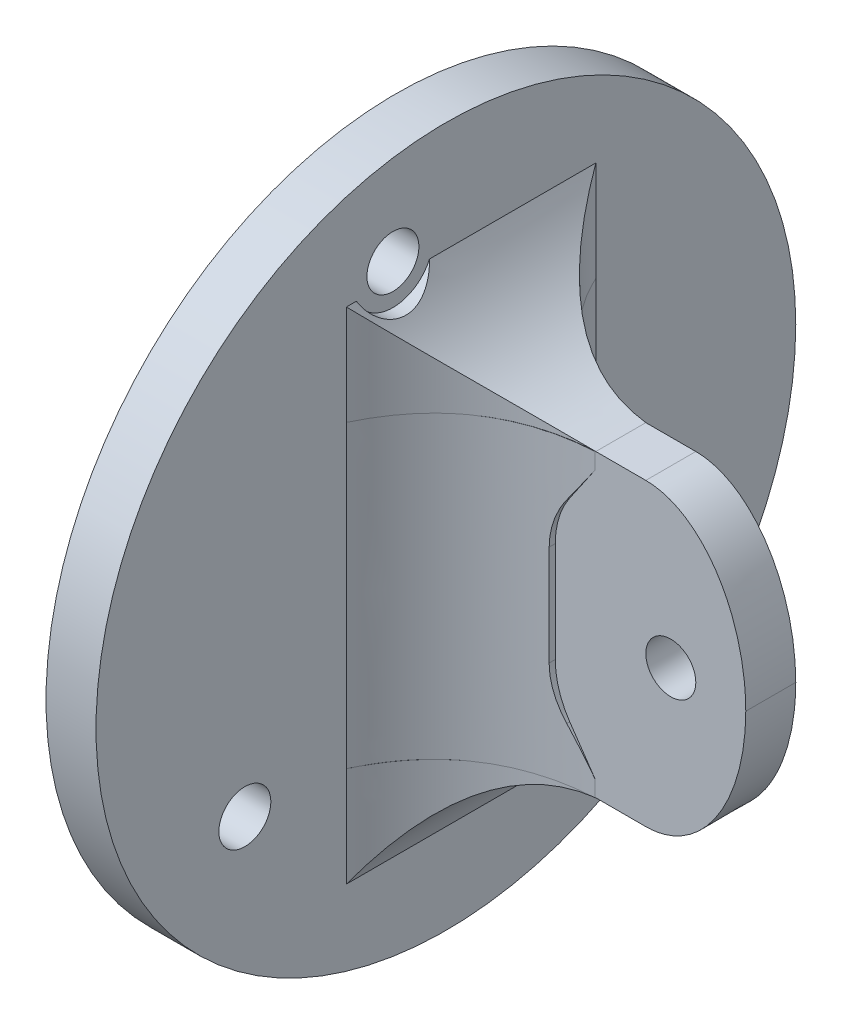
SolidWorks part; units mm, degrees
ref_plane "Ebene vorne" through (0, 0, 0) normal (0, 0, 1) x (1, 0, 0)
ref_plane "Ebene oben" through (0, 0, 0) normal (0, 1, 0) x (1, 0, 0)
ref_plane "Ebene rechts" through (0, 0, 0) normal (1, 0, 0) x (0, 0, -1)
sketch "Skizze1" plane through (0, 0, 0) normal (1, 0, 0) x (0, 0, -1)
  line L5 (-48.2966, 43.3868) -> (51.7034, 43.3868)
  line L6 (-48.2966, 43.3868) -> (-48.2966, -56.6132)
  line L7 (-48.2966, -56.6132) -> (51.7034, -56.6132)
  line L8 (51.7034, 43.3868) -> (51.7034, -56.6132)
  dimension "D1" = 100
  dimension "D2" = 100
extrude "Aufsatz-Linear austragen1" add sketch "Skizze1" along normal blind 5
sketch "Skizze4" plane through (0, 0, 0) normal (-1, 0, 0) x (0, 0, 1)
  line L1 (-51.7034, -56.6132) -> (-51.7034, 43.3868) construction
  circle A0 centre (3.5966, 30) radius 2.6
  circle A1 centre (18.4065, -10.6899) radius 2.6
  circle A2 centre (-24.2369, -3.1707) radius 2.6
  point P12 (-0.7446, 5.3798)
  point P13 (-1.7034, 0)
  dimension "D1" = 5.2
  dimension "D2" = 30
  dimension "D3" = 55.3
  dimension "D4" = 3
extrude "Schnitt-Linear austragen1" cut sketch "Skizze4" against normal blind 10
ref_plane "Ebene1" through (0, 0, -1.7034) normal (0, 0, -1) x (-1, 0, 0)
ref_plane "Ebene2" through (0, -6.6132, 0) normal (0, 1, 0) x (1, 0, 0)
sketch "Skizze5" plane through (5, 0, 0) normal (1, 0, 0) x (0, 0, -1)
  line L0 (1.7034, -2.75) -> (1.7034, 2.75) construction
  line L4 (2.75, -6.6132) -> (-2.75, -6.6132) construction
  line L5 (-48.2966, 43.3868) -> (51.7034, 43.3868)
  line L6 (51.7034, 43.3868) -> (51.7034, -56.6132)
  line L7 (51.7034, -56.6132) -> (-48.2966, -56.6132)
  line L8 (-48.2966, -56.6132) -> (-48.2966, 43.3868)
  circle A1 centre (1.7034, 4.3868) radius 35
  dimension "D1" = 70
  dimension "D2" = 0
  dimension "D3" = 11
extrude "Schnitt-Linear austragen2" cut sketch "Skizze5" against normal blind 10
sketch "Skizze6" plane through (5, 0, 0) normal (1, 0, 0) x (0, 0, -1)
  line L0 (1.7034, -55) -> (1.7034, 55) construction
  line L1 (1.7034, 18.3868) -> (6.7034, 18.3868)
  line L2 (1.7034, 18.3868) -> (1.7034, -11.6132)
  line L3 (1.7034, -11.6132) -> (6.7034, -11.6132)
  line L4 (6.7034, 18.3868) -> (6.7034, -11.6132)
  line L6 (55, -6.6132) -> (-55, -6.6132) construction
  dimension "D1" = 5
  dimension "D2" = 30
  dimension "D3" = 0
  dimension "D4" = 5
extrude "Aufsatz-Linear austragen2" add sketch "Skizze6" along normal blind 30
sketch "Skizze7" plane through (0, 0, -1.7034) normal (0, 0, 1) x (1, 0, 0)
  line L0 (35, 18.3868) -> (5, 18.3868) construction
  line L1 (35, 18.3868) -> (35, -11.6132) construction
  circle A0 centre (27.5, 3.3868) radius 2.5
  dimension "D1" = 5
  dimension "D2" = 15
  dimension "D3" = 7.5
extrude "Schnitt-Linear austragen3" cut sketch "Skizze7" against normal up to next
sketch "Skizze8" plane through (0, 18.3868, 0) normal (0, 1, 0) x (1, 0, 0)
  line L0 (4.9664, 1.6778) -> (19.9664, 1.6778)
  line L1 (4.9664, 1.6778) -> (4.9664, -8.3222)
  line L2 (5, 6.7034) -> (20, 6.7034)
  line L3 (35, 6.7034) -> (5, 6.7034) construction
  line L4 (5, 6.7034) -> (5, 16.7034)
  spline S0 degree 2 poles (4.9664, -8.3222) (9.3262, 1.0221) (19.9664, 1.6778) knots 0 0 0 1 1 1
  spline S1 degree 2 poles (5, 16.7034) (9.3598, 7.3591) (20, 6.7034) knots 0 0 0 1 1 1
  dimension "D1" = 10
  dimension "D2" = 15
  dimension "D3" = 15
  dimension "D4" = 10
  dimension "D5" = 5
  dimension "D6" = 5
  dimension "D7" = 3.5
  dimension "D8" = 3.5
extrude "Aufsatz-Linear austragen3" add sketch "Skizze8" against normal blind 30
sketch "Skizze10" plane through (0, 0, -6.7034) normal (0, 0, -1) x (-1, 0, 0)
  line L0 (-20, 18.3868) -> (-5, 18.3868)
  line L1 (-5, 18.3868) -> (-5, 28.3868)
  line L2 (-20, -11.6132) -> (-5, -11.6132)
  line L3 (-5, -11.6132) -> (-5, -21.6132)
  spline S0 degree 2 poles (-5, 28.3868) (-9.3598, 19.0425) (-20, 18.3868) knots 0 0 0 1 1 1
  spline S1 degree 2 poles (-20, -11.6132) (-9.3598, -12.2689) (-5, -21.6132) knots 0 0 0 1 1 1
  dimension "D1" = 10
  dimension "D2" = 15
  dimension "D3" = 3.5
  dimension "D4" = 5
  dimension "D5" = 10
  dimension "D6" = 15
  dimension "D7" = 3.5
  dimension "D8" = 5
extrude "Aufsatz-Linear austragen4" add sketch "Skizze10" against normal blind 15 and the other way blind 10
sketch "Skizze11" plane through (0, 18.3868, 0) normal (0, -1, 0) x (1, 0, 0)
  line L0 (5, 8.2966) -> (19.3696, 8.2966)
  line L1 (20, 8.2966) -> (5, 8.2966) construction
  line L2 (19.3696, 8.2966) -> (20, -1.7034)
  line L3 (5, -16.7034) -> (20, -16.7034)
  line L4 (20, -16.7034) -> (20, -6.7034)
  line L5 (20, -16.7034) -> (20, -6.7034) construction
  line L6 (5, 8.2966) -> (5, 8.2506)
  parabola Q0 (20, -6.7034) -> (5, -16.7034) focus (14.8919, -15.9918) apex (10.4586, -9.8585) construction
  parabola Q3 (20, -6.7034) -> (5, -16.7034) focus (14.8919, -15.9918) apex (10.4586, -9.8585) construction
  parabola Q4 (5, 8.2506) -> (19.9664, -1.6778) focus (14.8584, 7.6106) apex (10.425, 1.4773) construction
  spline S0 degree 2 poles (5, 8.2506) (9.4609, -1.0923) (20, -1.7034) knots 0 0 0 1 1 1
  spline S1 degree 2 poles (5, -16.7034) (9.4353, -7.3043) (20, -6.7034) knots 0 0 0 1 1 1
extrude "Schnitt-Linear austragen5" cut sketch "Skizze11" against normal blind 10 body kept at (0, 4.3868, -36.7034)
sketch "Skizze12" plane through (0, -11.6132, 0) normal (0, 1, 0) x (1, 0, 0)
  line L0 (20, 6.7034) -> (20, 16.7034)
  line L1 (20, 16.7034) -> (5, 16.7034)
  line L5 (5, -8.2966) -> (20, -8.2966)
  line L6 (20, -8.2966) -> (20, 1.7034)
  line L7 (20, 1.7034) -> (20, -8.2966) construction
  line L8 (5, -8.2966) -> (5, -8.2504)
  parabola Q1 (20, 6.7034) -> (5, 16.7034) focus (14.8919, 15.9918) apex (10.4586, 9.8585) construction
  parabola Q2 (5, -8.2506) -> (19.9664, 1.6778) focus (14.8584, -7.6106) apex (10.425, -1.4773) construction
  spline S0 degree 2 poles (5, -8.2504) (9.461, 1.0923) (20, 1.7034) knots 0 0 0 1 1 1
  spline S1 degree 2 poles (20, 6.7034) (9.4353, 7.3043) (5, 16.7034) knots 0 0 0 1 1 1
extrude "Schnitt-Linear austragen6" cut sketch "Skizze12" against normal blind 10
sketch "Skizze13" plane through (5, 0, 0) normal (1, 0, 0) x (0, 0, -1)
  circle A0 centre (-3.5966, 30) radius 4
  dimension "D1" = 8
extrude "Schnitt-Linear austragen7" cut sketch "Skizze13" along normal blind 5
fillet "Verrundung1" radius 10 1 edges at (35, 18.3868, -4.2034) second distance 15 first distance on face at (27.5, 18.3868, -4.2034)
fillet "Verrundung2" radius 10 1 edges at (35, -11.6132, -4.2034) second distance 15 first distance on face at (27.5, -11.6132, -4.2034)
sketch "Skizze14" plane through (0, 0, -1.7034) normal (0, 0, 1) x (1, 0, 0)
  line L3 (19.9664, -11.6132) -> (19.9664, 18.3868) construction
  line L9 (19.9664, 16.7868) -> (17.4176, 13.0782)
  line L11 (15.9664, -1.6345) -> (15.9664, 8.4047)
  line L14 (17.4171, -6.305) -> (19.9664, -10.0132)
  line L15 (19.9664, -10.0132) -> (19.9664, 16.7868)
  arc A0 (15.9664, 8.4047) -> (17.4176, 13.0782) centre (24.2176, 8.4047) cw
  arc A1 (15.9664, -1.6345) -> (17.4171, -6.305) centre (24.2106, -1.6345) ccw
  point P0 (19.9664, -10.0132)
  dimension "D1" = 1.6
  dimension "D2" = 34.509
  dimension "D3" = 1.6
  dimension "D4" = 34.5
  dimension "D5" = 4
  dimension "D6" = 4.5
  dimension "D7" = 4.5
extrude "Schnitt-Linear austragen8" cut sketch "Skizze14" along normal blind 10
